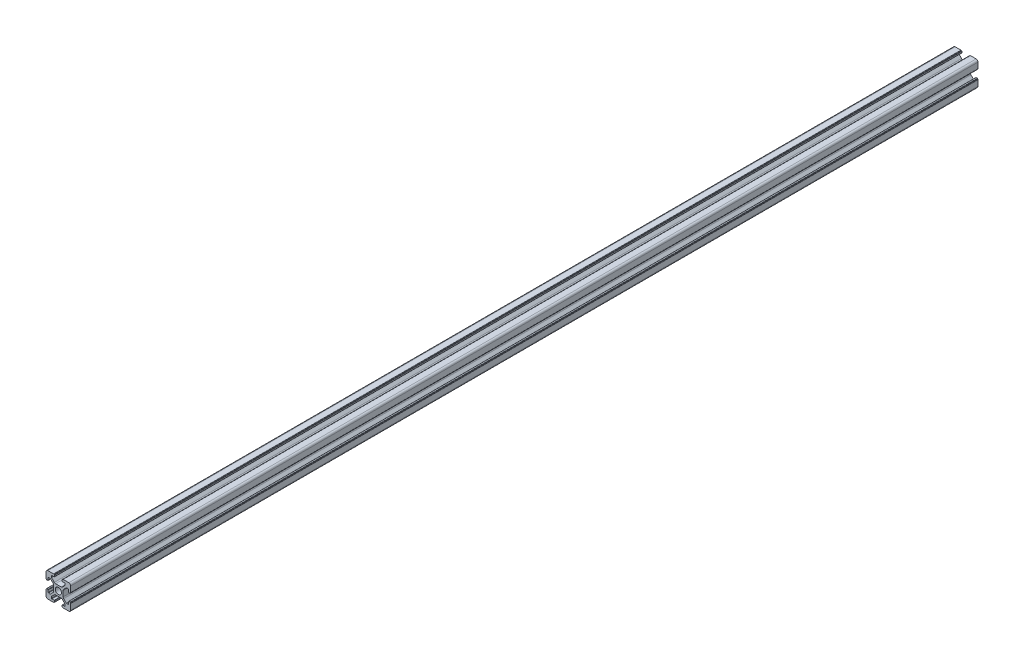
SolidWorks part; units mm, degrees
material "1060 Alloy"
ref_plane "Front Plane" through (0, 0, 0) normal (0, 0, 1) x (1, 0, 0)
ref_plane "Top Plane" through (0, 0, 0) normal (0, 1, 0) x (1, 0, 0)
ref_plane "Right Plane" through (0, 0, 0) normal (1, 0, 0) x (0, 0, -1)
sketch "Sketch1" plane through (0, 0, 0) normal (0, 0, 1) x (1, 0, 0)
  line L0 (3.8995, 3.9005) -> (10.4604, 10.4604) construction
  line L2 (-3.9002, 2.2177) -> (-3.9002, -2.2208)
  line L5 (-3.9005, 3.899) -> (3.9001, -3.8986) construction
  line L6 (-3.9, -3.901) -> (3.8995, 3.9005) construction
  line L7 (-0.0002, 10) -> (-0.0002, -9.9996) construction
  line L8 (-0.0002, -9.9996) -> (-0.0002, 10) construction
  line L9 (5.5006, 6.5619) -> (3.2793, 4.3405)
  line L14 (-10.0002, 9.9996) -> (9.9994, -10) construction
  line L15 (-9.9999, -10.0001) -> (9.9998, 10) construction
  line L16 (6.5613, 5.5012) -> (4.3401, 3.28)
  line L17 (-5.5002, 6.5603) -> (-3.279, 4.3391)
  line L18 (-6.5609, 5.4996) -> (-4.3395, 3.2783)
  line L19 (7.9206, 5.5012) -> (6.5613, 5.5012)
  line L20 (8.2006, 3.3812) -> (8.2006, 5.2212)
  line L21 (9.4206, 3.1012) -> (8.4806, 3.1012)
  line L22 (9.7006, 3.6012) -> (9.7006, 3.3812)
  line L23 (-8.5002, 9.9996) -> (-3.8802, 9.9996)
  line L24 (-3.6002, 9.7196) -> (-3.6002, 9.6996)
  line L25 (-3.6002, 9.6996) -> (-3.3802, 9.6996)
  line L26 (-3.1002, 9.4196) -> (-3.1002, 8.4796)
  line L27 (-3.3802, 8.1996) -> (-5.2202, 8.1996)
  line L28 (-5.5002, 7.9196) -> (-5.5002, 6.5603)
  line L29 (-7.9202, 5.4996) -> (-6.5609, 5.4996)
  line L30 (-8.2002, 3.3796) -> (-8.2002, 5.2196)
  line L31 (-9.4202, 3.0996) -> (-8.4802, 3.0996)
  line L32 (-9.7202, 3.5996) -> (-9.7002, 3.5996)
  line L33 (-9.7002, 3.5996) -> (-9.7002, 3.3796)
  line L34 (-10.0002, 8.4996) -> (-10.0002, 3.8796)
  line L35 (10.0006, 8.5012) -> (10.0006, 3.8812)
  line L36 (8.5006, 10.0012) -> (3.8806, 10.0012)
  line L37 (3.6006, 9.7012) -> (3.3806, 9.7012)
  line L38 (3.1006, 9.4212) -> (3.1006, 8.4812)
  line L39 (3.3806, 8.2012) -> (5.2206, 8.2012)
  line L40 (5.5006, 7.9212) -> (5.5006, 6.5619)
  line L41 (6.5629, -5.4996) -> (4.3415, -3.2783)
  line L42 (5.5022, -6.5603) -> (3.281, -4.3391)
  line L43 (5.5022, -7.9196) -> (5.5022, -6.5603)
  line L44 (3.3822, -8.1996) -> (5.2222, -8.1996)
  line L45 (3.1022, -9.4196) -> (3.1022, -8.4796)
  line L46 (3.6022, -9.6996) -> (3.3822, -9.6996)
  line L47 (8.5022, -9.9996) -> (3.8822, -9.9996)
  line L48 (10.0022, -8.4996) -> (10.0022, -3.8796)
  line L49 (9.7022, -3.5996) -> (9.7022, -3.3796)
  line L50 (9.4222, -3.0996) -> (8.4822, -3.0996)
  line L51 (8.2022, -3.3796) -> (8.2022, -5.2196)
  line L52 (7.9222, -5.4996) -> (6.5629, -5.4996)
  line L53 (-5.4986, -6.5619) -> (-3.2773, -4.3405)
  line L54 (-6.5593, -5.5012) -> (-4.3395, -3.2814)
  line L55 (-7.9186, -5.5012) -> (-6.5593, -5.5012)
  line L56 (-8.1986, -3.3812) -> (-8.1986, -5.2212)
  line L57 (-9.4186, -3.1012) -> (-8.4786, -3.1012)
  line L58 (-9.6986, -3.6012) -> (-9.6986, -3.3812)
  line L59 (-9.9986, -8.5012) -> (-9.9986, -3.8812)
  line L60 (-8.4986, -10.0012) -> (-3.8786, -10.0012)
  line L61 (-3.5986, -9.7012) -> (-3.3786, -9.7012)
  line L62 (-3.0986, -9.4212) -> (-3.0986, -8.4812)
  line L63 (-3.3786, -8.2012) -> (-5.2186, -8.2012)
  line L64 (-5.4986, -7.9212) -> (-5.4986, -6.5619)
  line L65 (-2.233, 3.8998) -> (2.2187, 3.9012)
  line L66 (3.9008, 2.234) -> (3.9022, -2.2177)
  line L67 (2.235, -3.8998) -> (-2.2167, -3.9012)
  line L68 (3.6006, 9.7212) -> (3.6006, 9.6996)
  line L69 (9.7006, 3.6012) -> (9.7206, 3.6012)
  line L70 (-9.6986, -3.6012) -> (-9.7186, -3.6012)
  line L71 (-3.5986, -9.7012) -> (-3.5986, -9.7212)
  line L72 (3.6022, -9.6996) -> (3.6022, -9.7196)
  line L73 (9.7222, -3.5996) -> (9.7022, -3.5996)
  arc A0 (-3.6002, 9.7196) -> (-3.8802, 9.9996) centre (-3.8802, 9.7196) ccw
  arc A1 (-3.3802, 9.6996) -> (-3.1002, 9.4196) centre (-3.3802, 9.4196) cw
  arc A2 (-3.1002, 8.4796) -> (-3.3802, 8.1996) centre (-3.3802, 8.4796) cw
  arc A3 (-10.0002, 8.4996) -> (-8.5002, 9.9996) centre (-8.5002, 8.4996) cw
  arc A4 (-8.2002, 3.3796) -> (-8.4802, 3.0996) centre (-8.4802, 3.3796) cw
  arc A5 (-9.4202, 3.0996) -> (-9.7002, 3.3796) centre (-9.4202, 3.3796) cw
  arc A6 (-9.7202, 3.5996) -> (-10.0002, 3.8796) centre (-9.7202, 3.8796) cw
  arc A7 (-3.279, 4.3391) -> (-2.233, 3.8998) centre (-2.2183, 5.3997) ccw
  arc A8 (-4.3395, 3.2783) -> (-3.9002, 2.2177) centre (-5.4002, 2.2177) cw
  arc A9 (-7.9202, 5.4996) -> (-8.2002, 5.2196) centre (-7.9202, 5.2196) ccw
  arc A10 (-5.2202, 8.1996) -> (-5.5002, 7.9196) centre (-5.2202, 7.9196) ccw
  arc A12 (-4.3395, -3.2814) -> (-3.9002, -2.2208) centre (-5.4002, -2.2208) ccw
  arc A13 (8.2006, 5.2212) -> (7.9206, 5.5012) centre (7.9206, 5.2212) ccw
  arc A14 (8.4806, 3.1012) -> (8.2006, 3.3812) centre (8.4806, 3.3812) cw
  arc A15 (9.7006, 3.3812) -> (9.4206, 3.1012) centre (9.4206, 3.3812) cw
  arc A16 (9.7206, 3.6012) -> (10.0006, 3.8812) centre (9.7206, 3.8812) ccw
  arc A17 (8.5006, 10.0012) -> (10.0006, 8.5012) centre (8.5006, 8.5012) cw
  arc A18 (3.6006, 9.7212) -> (3.8806, 10.0012) centre (3.8806, 9.7212) cw
  arc A19 (3.1006, 9.4212) -> (3.3806, 9.7012) centre (3.3806, 9.4212) cw
  arc A20 (3.3806, 8.2012) -> (3.1006, 8.4812) centre (3.3806, 8.4812) cw
  arc A21 (5.5006, 7.9212) -> (5.2206, 8.2012) centre (5.2206, 7.9212) ccw
  arc A22 (3.2793, 4.3405) -> (2.2187, 3.9012) centre (2.2187, 5.4012) cw
  arc A23 (4.3401, 3.28) -> (3.9008, 2.234) centre (5.4007, 2.2193) ccw
  arc A25 (5.2222, -8.1996) -> (5.5022, -7.9196) centre (5.2222, -7.9196) ccw
  arc A26 (3.1022, -8.4796) -> (3.3822, -8.1996) centre (3.3822, -8.4796) cw
  arc A27 (3.3822, -9.6996) -> (3.1022, -9.4196) centre (3.3822, -9.4196) cw
  arc A28 (3.6022, -9.7196) -> (3.8822, -9.9996) centre (3.8822, -9.7196) ccw
  arc A29 (10.0022, -8.4996) -> (8.5022, -9.9996) centre (8.5022, -8.4996) cw
  arc A30 (9.7222, -3.5996) -> (10.0022, -3.8796) centre (9.7222, -3.8796) cw
  arc A31 (9.4222, -3.0996) -> (9.7022, -3.3796) centre (9.4222, -3.3796) cw
  arc A32 (8.2022, -3.3796) -> (8.4822, -3.0996) centre (8.4822, -3.3796) cw
  arc A33 (7.9222, -5.4996) -> (8.2022, -5.2196) centre (7.9222, -5.2196) ccw
  arc A34 (4.3415, -3.2783) -> (3.9022, -2.2177) centre (5.4022, -2.2177) cw
  arc A35 (3.281, -4.3391) -> (2.235, -3.8998) centre (2.2203, -5.3997) ccw
  circle A36 centre (0.001, -0.001) radius 2.5 construction
  arc A37 (-8.1986, -5.2212) -> (-7.9186, -5.5012) centre (-7.9186, -5.2212) ccw
  arc A38 (-8.4786, -3.1012) -> (-8.1986, -3.3812) centre (-8.4786, -3.3812) cw
  arc A39 (-9.6986, -3.3812) -> (-9.4186, -3.1012) centre (-9.4186, -3.3812) cw
  arc A40 (-9.7186, -3.6012) -> (-9.9986, -3.8812) centre (-9.7186, -3.8812) ccw
  arc A41 (-8.4986, -10.0012) -> (-9.9986, -8.5012) centre (-8.4986, -8.5012) cw
  arc A42 (-3.5986, -9.7212) -> (-3.8786, -10.0012) centre (-3.8786, -9.7212) cw
  arc A43 (-3.0986, -9.4212) -> (-3.3786, -9.7012) centre (-3.3786, -9.4212) cw
  arc A44 (-3.3786, -8.2012) -> (-3.0986, -8.4812) centre (-3.3786, -8.4812) cw
  arc A45 (-5.4986, -7.9212) -> (-5.2186, -8.2012) centre (-5.2186, -7.9212) ccw
  arc A46 (-3.2773, -4.3405) -> (-2.2167, -3.9012) centre (-2.2167, -5.4012) cw
  arc A48 (-4.3381, -3.28) -> (-3.8988, -2.234) centre (-5.3987, -2.2193) ccw [skipped]
  point P0 (0, 0)
  point P9 (-0.0002, 0.0002)
  point P12 (-0.0003, -0.0003)
  point P43 (-3.6002, 9.9996)
  point P46 (-3.1002, 9.6996)
  point P49 (-3.1002, 8.1996)
  point P55 (-8.2002, 3.0996)
  point P58 (-9.7002, 3.0996)
  point P61 (-10.0002, 3.5996)
  point P64 (-2.8395, 3.8996)
  point P67 (-3.9002, 2.839)
  point P70 (-8.2002, 5.4996)
  point P73 (-5.5002, 8.1996)
  point P184 (0.001, 0)
  dimension "D14" = 0.28
  dimension "D15" = 0.28
  dimension "D16" = 0.28
  dimension "D17" = 1.5
  dimension "D18" = 0.28
  dimension "D19" = 1.5
  dimension "D20" = 1.5
  dimension "D21" = 0.28
  dimension "D23" = 5
  dimension "D27" = 1.5
  dimension "D1" = 7.8
  dimension "D2" = 7.8
  dimension "D3" = 3.1
  dimension "D4" = 3.6
  dimension "D5" = 20
  dimension "D6" = 20
  dimension "D7" = 0.75
  dimension "D8" = 1.8
  dimension "D9" = 5.5
  dimension "D10" = 6.4
  dimension "D11" = 6.4
  dimension "D12" = 3.7627
  dimension "D13" = 0.3
  dimension "D24" = 4.62
  dimension "D25" = 3.9005
  dimension "D26" = 7.801
  dimension "D22" = 4
extrude "Boss-Extrude1" add sketch "Sketch1" along normal blind 735 contours L53 A46 L67 A35 L42 L43 A25 L44 A26 L45 A27 L46 L72 A28 L47 A29 L48 A30 L73 L49 A31 L50 A32 L51 A33 L52 L41 A34 L66 A23 L16 L19 A13 L20 A14 L21 A15 L22 L69 A16 L35 A17 L36 A18 L68 L37 A19 L38 A20 region at (0.0009, 0, 0)
sketch3d "3DSketch2"
  circle A0 centre (0, 0, 0) radius 2.5
  point P2 (0, 0, 2.5)
extrude "Cut-Extrude1" cut sketch "3DSketch2" along direction (0, 0, 1) on the side of the normal through all contours A0
